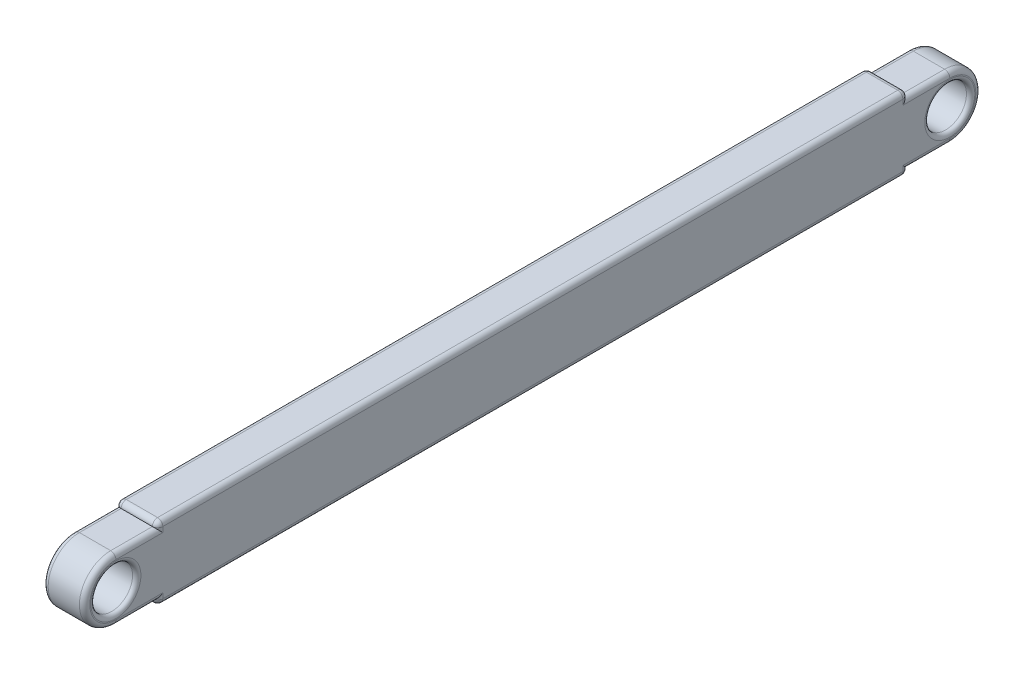
SolidWorks part; units mm, degrees
ref_plane "Front Plane" through (0, 0, 0) normal (0, 0, 1) x (1, 0, 0)
ref_plane "Top Plane" through (0, 0, 0) normal (0, 1, 0) x (1, 0, 0)
ref_plane "Right Plane" through (0, 0, 0) normal (1, 0, 0) x (0, 0, -1)
sketch "Sketch1" plane through (0, 0, 0) normal (1, 0, 0) x (0, 0, -1)
  line L0 (0, 0) -> (0, -0.125)
  line L1 (0, 0) -> (18, 0)
  line L2 (0, 0) -> (0, -1.75) construction
  line L3 (0, -1.75) -> (18, -1.75)
  line L4 (18, 0) -> (18, -1.75) construction
  line L5 (0, -0.125) -> (-1, -0.125)
  line L6 (0, -0.125) -> (0, -1.625) construction
  line L7 (0, -1.625) -> (-1, -1.625)
  line L8 (-1, -0.125) -> (-1, -1.625) construction
  line L9 (18, -0.125) -> (19, -0.125)
  line L10 (18, -0.125) -> (18, -1.625) construction
  line L11 (18, -1.625) -> (19, -1.625)
  line L12 (19, -0.125) -> (19, -1.625) construction
  line L13 (0, -1.625) -> (0, -1.75)
  line L14 (18, 0) -> (18, -0.125)
  line L15 (18, -1.625) -> (18, -1.75)
  line L16 (0, -0.875) -> (-1, -0.875) construction
  line L17 (18, -0.875) -> (19, -0.875) construction
  circle A0 centre (-1, -0.875) radius 0.5
  arc A1 (-1, -1.625) -> (-1, -0.125) centre (-1, -0.875) cw
  circle A2 centre (19, -0.875) radius 0.5
  arc A3 (19, -0.125) -> (19, -1.625) centre (19, -0.875) cw
  point P12 (0, 0)
  point P20 (0, 0)
  dimension "D1" = 1
  dimension "D4" = 1
  dimension "D2" = 1.5
  dimension "D3" = 1.5
  dimension "D5" = 20
  dimension "D6" = 1.75
  dimension "D7" = 1
  dimension "D8" = 1
extrude "Boss-Extrude1" add sketch "Sketch1" along normal blind 1
fillet "Fillet1" radius 0.125 16 edges at (1, -1.75, -9) (0, -1.75, -9) (0, 0, -9) (1, 0, -9) (0, -1.625, -18.5) (0, -0.875, -19.75) (1, -1.625, -18.5) (1, -0.875, -19.75) (0, -1.625, 0.5) (0, -0.875, 1.75) (1, -1.625, 0.5) (1, -0.875, 1.75) (0, -0.125, -18.5) (1, -0.125, -18.5) (0, -0.125, 0.5) (1, -0.125, 0.5)
fillet "Fillet2" radius 0.1 4 edges at (0, -0.875, 0.5) (1, -0.875, 0.5) (0, -0.875, -19.5) (1, -0.875, -19.5)
fillet "Fillet3" radius 0.125 20 edges at (1, -1.5625, 0) (0.9634, -1.7134, 0) (0.5, -1.75, 0) (0.0366, -1.7134, 0) (1, -0.1875, 0) (0.9634, -0.0366, 0) (0.5, 0, 0) (0.0366, -0.0366, 0) (1, -1.5625, -18) (0.9634, -1.7134, -18) (0.5, -1.75, -18) (0.0366, -1.7134, -18) (1, -0.1875, -18) (0.9634, -0.0366, -18) (0.5, 0, -18) (0.0366, -0.0366, -18) (0, -1.5625, 0) (0, -0.1875, 0) (0, -1.5625, -18) (0, -0.1875, -18)
